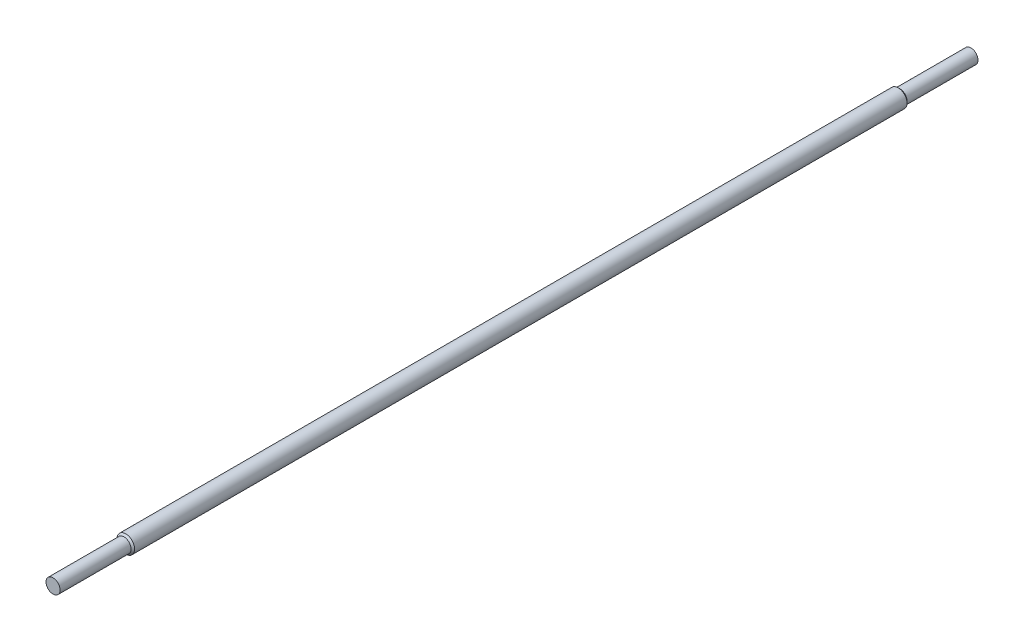
SolidWorks part; units mm, degrees
material "Gray Cast Iron"
ref_plane "Front" through (0, 0, 0) normal (0, 0, 1) x (1, 0, 0)
ref_plane "Top" through (0, 0, 0) normal (0, 1, 0) x (1, 0, 0)
ref_plane "Right" through (0, 0, 0) normal (1, 0, 0) x (0, 0, -1)
sketch "Sketch1" plane through (0, 0, 0) normal (0, 0, 1) x (1, 0, 0)
  circle A0 centre (0, 0) radius 15.875
  dimension "D1" = 31.75
extrude "Boss-Extrude1" add sketch "Sketch1" along normal mid plane 1651
sketch "Sketch2" plane through (0, 0, 825.5) normal (0, 0, 1) x (1, 0, 0)
  circle A0 centre (0, 0) radius 12.7
  circle A1 centre (0, 0) radius 22.7111
  dimension "D1" = 25.4
extrude "Cut-Extrude1" cut sketch "Sketch2" against normal blind 127
mirror "Mirror1" about plane through (0, 0, 0) normal (0, 0, 1) of "Cut-Extrude1"
chamfer "Chamfer1" distance 3.81 angle 45 2 edges at (-15.875, 0, -698.5) (15.875, 0, 698.5)
